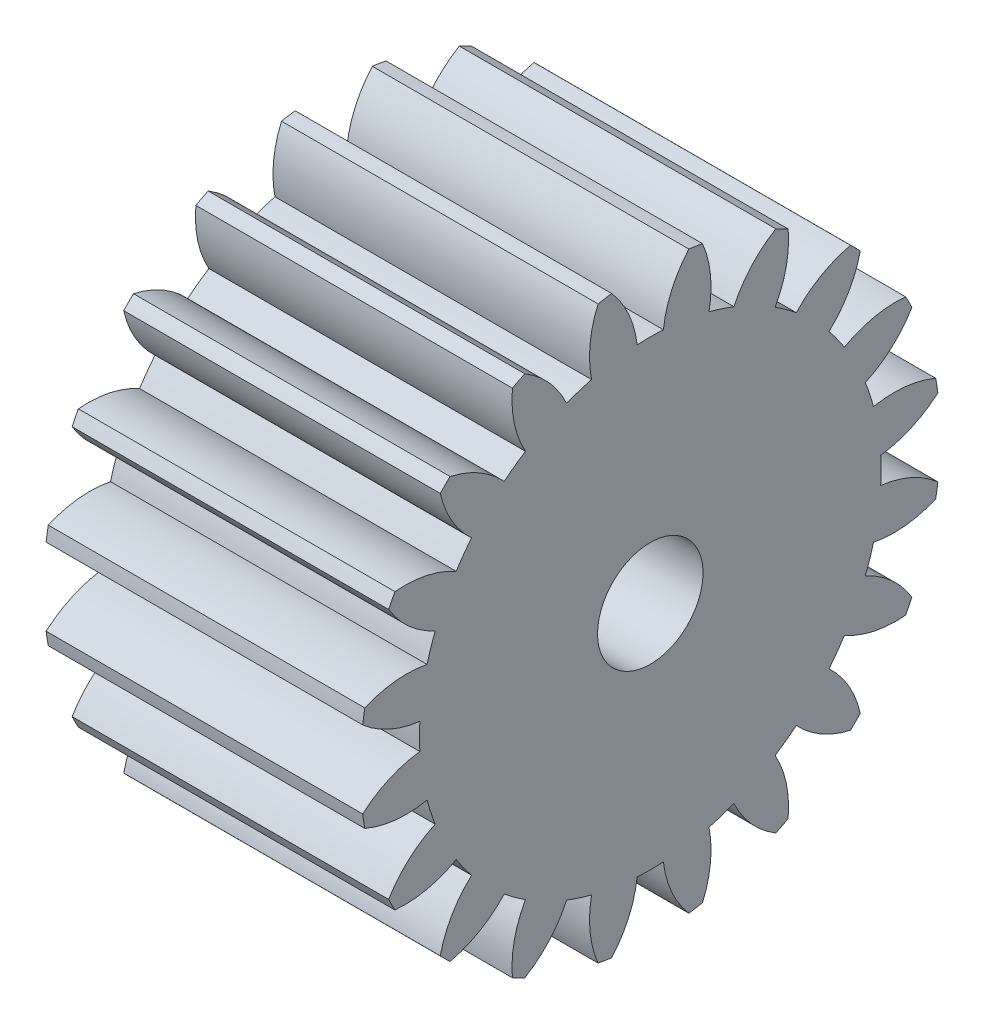
SolidWorks part; units mm, degrees
ref_plane "Plane1" through (0, 0, 0) normal (0, 0, 1) x (1, 0, 0)
ref_plane "Plane2" through (0, 0, 0) normal (0, 1, 0) x (1, 0, 0)
ref_plane "Plane3" through (0, 0, 0) normal (1, 0, 0) x (0, 0, -1)
other "Configuration Table"
sketch "HoldingSke" plane through (0, 0, 0) normal (0, 1, 0) x (1, 0, 0)
  line L0 (0, 0) -> (0.7518, -0.2736)
  line L1 (-15, 0) -> (100, 0) construction
  line L2 (0, 0) -> (-2.1039, 2.3779)
  line L3 (0, 0) -> (-11.863, 4.5341)
  line L4 (0, 0) -> (8.1152, 2.9537)
  line L5 (0, 0) -> (-46.8476, -17.4728)
  line L6 (0, 0) -> (-12.4344, -8.3896)
  line L7 (-2.1039, 2.3779) -> (8.6586, 51.2059)
  line L8 (-76.2, 54.61) -> (-75.3, 54.61)
  line L9 (-71.009, 38.7566) -> (-53.1078, 45.2721)
  line L10 (-76.2, 71.12) -> (104.1128, 71.12)
  line L11 (0, 0) -> (-15, 0)
  line L12 (-76.2, 101.6) -> (-76.155, 101.6)
  line L13 (24.9733, 27.94) -> (52.9518, 28.4284)
  line L14 (24.9733, 27.94) -> (24.9743, 27.94)
  line L15 (24.9733, 27.94) -> (100.4006, 29.5858)
  line L16 (-63.627, -1.25) -> (-12.827, -1.25)
  circle A0 centre (0, 0) radius 2.5
  circle A1 centre (0, 0) radius 10.9365
  circle A2 centre (0, 0) radius 37.5
  circle A3 centre (0, 0) radius 2.5
  dimension "Num_teeth" = 20
  dimension "Pitch_radius" = 180.3128
  dimension "Width" = 15
  dimension "Thickness" = 15
sketch "BasProSke" plane through (0, 0, 0) normal (0, 1, 0) x (1, 0, 0)
  line L0 (-10, 0) -> (60, 0) construction
  line L1 (0, 0) -> (0, 13.75)
  line L2 (0, 0) -> (15, 0)
  line L3 (15, 0) -> (15, 13.75)
  line L4 (15, 13.75) -> (0, 13.75)
  dimension "Thickness" = 15
  dimension "Diameter" = 27.5
revolve "Base-Revolve" add sketch "BasProSke" angle 360 about L0
sketch "TooCutSke" plane through (0, 0, 0) normal (1, 0, 0) x (0, 0, -1)
  line L1 (0, 0) -> (0, 107) construction
  line L2 (0, 0) -> (-1.0594, 12.455) construction
  line L3 (0, 0) -> (-3.9007, 24.6278) construction
  line L4 (-1.0594, 12.455) -> (-1.9503, 12.3139) construction
  arc A0 (0.6211, 10.9188) -> (-0.6211, 10.9188) centre (0, 0) ccw
  arc A1 (1.8466, 13.6511) -> (-1.8466, 13.6511) centre (0, 0) ccw
  circle A2 centre (0, 0) radius 12.5 construction
  circle A3 centre (0, 0) radius 11.7462 construction
  arc A4 (-0.6211, 10.9188) -> (-1.8466, 13.6511) centre (-5.5866, 10.3326) ccw
  arc A5 (1.8466, 13.6511) -> (0.6211, 10.9188) centre (5.5866, 10.3326) ccw
extrude "ToothCut" cut sketch "TooCutSke" along normal through all
fillet "Breaks" [suppressed] radius 0.025 tangent propagation no
fillet "RootFillets" [suppressed] radius 0.3135
pattern_circular "TeethCuts" count 20 every 18 about axis through (-10, 0, 0) along (1, 0, 0) of "ToothCut", "RootFillets", "Breaks"
sketch "HubNeaOneSke" plane through (0, 0, 0) normal (-1, 0, 0) x (0, 0, 1)
  circle A0 centre (0, 0) radius 10.9365
  dimension "Diameter" = 21.873
extrude "HubNearOne" [suppressed] add sketch "HubNeaOneSke" along normal blind 35.0001
sketch "HubNeaBotSke" plane through (0, 0, 0) normal (-1, 0, 0) x (0, 0, 1)
  circle A0 centre (0, 0) radius 10.9365
  dimension "Diameter" = 21.873
extrude "HubNearBoth" [suppressed] add sketch "HubNeaBotSke" along normal blind 17.5
ref_plane "FarPln" through (15, 0, 0) normal (1, 0, 0) x (0, 0, -1)
sketch "HubFarSke" plane through (15, 0, 0) normal (1, 0, 0) x (0, 0, -1)
  circle A0 centre (0, 0) radius 10.9365
  dimension "Diameter" = 21.873
extrude "HubFar" [suppressed] add sketch "HubFarSke" along normal blind 17.5
sketch "BorSke" plane through (0, 0, 0) normal (1, 0, 0) x (0, 0, -1)
  circle A0 centre (0, 0) radius 2.5
  dimension "Diameter" = 5
extrude "Bore" cut sketch "BorSke" along normal mid plane 100.0001
sketch "KeySke" plane through (0, 0, 0) normal (1, 0, 0) x (0, 0, -1)
  line L0 (-1, 0) -> (-1, 3.4)
  line L1 (-1, 3.4) -> (1, 3.4)
  line L2 (1, 3.4) -> (1, 0)
  line L3 (0, 0) -> (0, 34) construction
  line L4 (-1, 0) -> (1, 0)
extrude "Keyway" [suppressed] cut sketch "KeySke" along normal mid plane 100.0001
pattern_circular "Keyway2" [suppressed] count 2 every 90 about axis through (-10, 0, 0) along (1, 0, 0)
equation "' \"Module@HoldingSke\" = 6.35"
equation "' \"Num_teeth@HoldingSke\" = 12"
equation "' \"Ap@HoldingSke\" =  20"
equation "' \"Ap@HoldingSke\" = 20"
equation "' \"Width@HoldingSke\" = 0.5 * 25.4"
equation "' \"Hub_dia@HoldingSke\"= 1 * 25.4"
equation "' \"Hub_dia@HoldingSke\" = 1 * 25.4"
equation "' \"Overall_len@HoldingSke\" = 1.0 * 25.4"
equation "' \"Bore@HoldingSke\" = 0.75 * 25.4"
equation "' \"T_dim@HoldingSke\" = 0.1 * 25.4"
equation "' \"Width@KeySke\" = 0.25 * 25.4"
equation "' \"Show_teeth@HoldingSke\" = 13"
equation "' \"Backlash@HoldingSke\" = 0.009 * 25.4"
equation "' \"Addendum_fac@HoldingSke\" = 1.0"
equation "' \"Dedendum_fac@HoldingSke\" = 1.25"
equation "' \"Dedendum_add@HoldingSke\" = 0.00005 * 25.4"
equation "' \"Clearance_fac@HoldingSke\" = 0.25"
equation "\"Pitch@HoldingSke\" = 1 / \"Module@HoldingSke\""
equation "\"Overcut_dia@TooCutSke\" = (\"Num_teeth@HoldingSke\" + 2 * \"Addendum_fac@HoldingSke\") / \"Pitch@HoldingSke\" + 0.002 * 25.4"
equation "\"Pitch_dia@TooCutSke\" = \"Num_teeth@HoldingSke\" / \"Pitch@HoldingSke\""
equation "\"Base_dia@TooCutSke\" = \"Num_teeth@HoldingSke\" / \"Pitch@HoldingSke\" * cos((\"Ap@HoldingSke\"  * 3.14159265 / 180))"
equation "\"Root_dia@TooCutSke\" = (\"Num_teeth@HoldingSke\" + 2) / \"Pitch@HoldingSke\" - 2 * (\"Addendum_fac@HoldingSke\" + \"Dedendum_fac@HoldingSke\") / \"Pitch@HoldingSke\" - \"Dedendum_add@HoldingSke\" * 2"
equation "\"Half_ang@TooCutSke\" = 180 / \"Num_teeth@HoldingSke\""
equation "\"Half_CT@TooCutSke\" = \"Num_teeth@HoldingSke\" / \"Pitch@HoldingSke\" * sin((3.14159265 / 2 / \"Num_teeth@HoldingSke\")) / 2 - 7 * \"Backlash@HoldingSke\" / 4"
equation "\"Flank_rad@TooCutSke\" = \"Num_teeth@HoldingSke\" / \"Pitch@HoldingSke\" / 5"
equation "\"Radius@RootFillets\" = \"Clearance_fac@HoldingSke\" / \"Pitch@HoldingSke\" + \"Dedendum_add@HoldingSke\""
equation "\"Break_rad@Breaks\" = 0.02 / \"Pitch@HoldingSke\""
equation "\"Thickness@HoldingSke\" = \"Width@HoldingSke\""
equation "\"OAL@HoldingSke\" = \"Thickness@HoldingSke\""
equation "\"MHD@HoldingSke\" = (\"Num_teeth@HoldingSke\" + 2) / \"Pitch@HoldingSke\" - 2 * (\"Addendum_fac@HoldingSke\" + \"Dedendum_fac@HoldingSke\")  / \"Pitch@HoldingSke\" - \"Dedendum_add@HoldingSke\" * 2"
equation "\"MBD@HoldingSke\" = (\"Num_teeth@HoldingSke\" + 2) / \"Pitch@HoldingSke\" - 2 * (\"Addendum_fac@HoldingSke\" + \"Dedendum_fac@HoldingSke\")  / \"Pitch@HoldingSke\" - \"Dedendum_add@HoldingSke\" * 2 - 0.002 * 25.4"
equation "\"MHD@HoldingSke\" = ((sgn( \"MHD@HoldingSke\" - \"Hub_dia@HoldingSke\" )-1)*( \"MHD@HoldingSke\" - \"Hub_dia@HoldingSke\" ))/-2+ \"Hub_dia@HoldingSke\""
equation "\"MBD@HoldingSke\" = ((sgn( \"MBD@HoldingSke\" - \"Bore@HoldingSke\" )-1)*( \"MBD@HoldingSke\" - \"Bore@HoldingSke\" ))/-2+ \"Bore@HoldingSke\""
equation "\"OAL@HoldingSke\" = ((sgn( \"OAL@HoldingSke\" - \"Overall_len@HoldingSke\" )+1)*( \"OAL@HoldingSke\" - \"Overall_len@HoldingSke\" ))/2 + \"Overall_len@HoldingSke\" + 0.000002 * 25.4"
equation "\"Num_teeth@TeethCuts\" = int( \"Show_teeth@HoldingSke\" ) + 1"
equation "\"Num_teeth@TeethCuts\" = ((sgn( \"Num_teeth@TeethCuts\" - \"Num_teeth@HoldingSke\" )-1)*( \"Num_teeth@TeethCuts\" - \"Num_teeth@HoldingSke\" ))/-2+ \"Num_teeth@HoldingSke\""
equation "\"Num_teeth@TeethCuts\" = ((sgn( \"Num_teeth@TeethCuts\" - 2.0)+1)*( \"Num_teeth@TeethCuts\" - 2.0))/2 +2.0"
equation "\"Angle@TeethCuts\" = 360.0 / \"Num_teeth@HoldingSke\""
equation "\"Diameter@BasProSke\" = (\"Num_teeth@HoldingSke\" + 2 * \"Addendum_fac@HoldingSke\") / \"Pitch@HoldingSke\""
equation "\"Thickness@BasProSke\"  = \"Thickness@HoldingSke\""
equation "' \"Fillet_rad@BasProSke\" =  \"Thickness@HoldingSke\" * 0.05"
equation "' \"Fillet_rad@BasProSke\" = \"Thickness@HoldingSke\" * 0.05"
equation "\"MHD@HoldingSke\" = ((sgn( \"MHD@HoldingSke\" - \"Root_dia@TooCutSke\" )-1)*( \"MHD@HoldingSke\" - \"Root_dia@TooCutSke\" ))/-2+ \"Root_dia@TooCutSke\""
equation "\"Diameter@HubNeaOneSke\" = \"MHD@HoldingSke\""
equation "\"Length@HubNearOne\" = \"OAL@HoldingSke\" - \"Thickness@BasProSke\""
equation "\"Diameter@HubNeaBotSke\" = \"MHD@HoldingSke\""
equation "\"Length@HubNearBoth\" = ( \"OAL@HoldingSke\" - \"Thickness@BasProSke\" ) / 2.0"
equation "\"Thickness@FarPln\" = \"Thickness@BasProSke\""
equation "\"Diameter@HubFarSke\" = \"MHD@HoldingSke\""
equation "\"Length@HubFar\" = ( \"OAL@HoldingSke\" - \"Thickness@BasProSke\" ) / 2.0"
equation "\"Diameter@BorSke\" = \"MBD@HoldingSke\""
equation "\"D1@Bore\" = \"OAL@HoldingSke\" * 2.0"
equation "\"D1@Keyway\" = \"OAL@HoldingSke\" * 2.0"
equation "\"Offset@KeySke\" = \"T_dim@HoldingSke\" + \"MBD@HoldingSke\" / 2.0"
